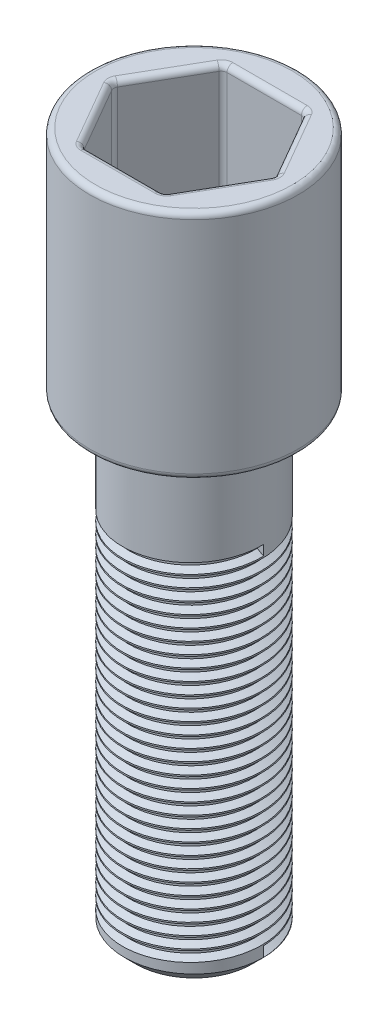
SolidWorks part; units mm, degrees
material "AISI 4140 Steel, quenched & tempered"
ref_plane "Front Plane" through (0, 0, 0) normal (1, 0, 0) x (0, 1, 0)
ref_plane "Top Plane" through (0, 0, 0) normal (0, 0, 1) x (0, 1, 0)
ref_plane "Right Plane" through (0, 0, 0) normal (0, 1, 0) x (-1, 0, 0)
sketch "Sketch1" plane through (0, 0, 0) normal (1, 0, 0) x (0, 1, 0)
  line L0 (-122.9929, 0) -> (42.9358, 0) construction
  line L1 (0, 23.268) -> (0, -20.4189) construction
  line L2 (10, 0) -> (10, 4.5)
  line L3 (10, 4.5) -> (0, 4.5)
  line L4 (0, 4.5) -> (0, 3)
  line L5 (0, 3) -> (-20, 3)
  line L6 (-20, 3) -> (-20, 0)
  line L7 (-20, 0) -> (10, 0)
  dimension "D1" = 10
  dimension "D2" = 9
  dimension "D3" = 6
  dimension "D4" = 20
revolve "Revolve1" add sketch "Sketch1" angle 360 about L0
sketch "Sketch2" plane through (0, 10, 0) normal (0, 1, 0) x (-1, 0, 0)
  line L1 (1.75, -3.0311) -> (3.5, 0)
  line L2 (3.5, 0) -> (1.75, 3.0311)
  line L3 (1.75, 3.0311) -> (-1.75, 3.0311)
  line L4 (-1.75, 3.0311) -> (-3.5, 0)
  line L5 (-3.5, 0) -> (-1.75, -3.0311)
  line L6 (-1.75, -3.0311) -> (1.75, -3.0311)
  circle A0 centre (0, 0) radius 3.0311 construction
  dimension "D1" = 3.5
extrude "Cut-Extrude1" cut sketch "Sketch2" against normal blind 8
ref_axis "Axis1" through (0, 16, 0) along (0, -1, 0)
thread "Thread2" pitch 0.5 method cut profile "Thread Profile2" start angle 0, offset 0.5, length 15, pitch 0.5, diameter 6
ref_plane "Plane2" through (3, -19.5, 0) normal (0, 0, 1) x (1, 0, 0)
sketch "Thread Profile2" plane through (3, -19.5, 0) normal (0, 0, 1) x (1, 0, 0)
  line L0 (0, 0) -> (0, 0.5) construction
  line L11 (0, 0) -> (0, 0.4375)
  line L12 (0, 0.4375) -> (-0.2706, 0.2812)
  line L13 (-0.2706, 0.2812) -> (-0.2706, 0.1562)
  line L15 (-0.2706, 0.1562) -> (0, 0)
  line L17 (-0.2706, 0.2187) -> (0, 0.2187) construction
  point P2 (0, 0)
  dimension "Pitch" = 0.5
  dimension "Profile_Angle" = 60
  dimension "Profile_Land" = 0.125
  dimension "Profile_Height" = 0.2706
chamfer "Chamfer1" distance 0.5 angle 45 1 edges at (0, -20, -3)
fillet "Fillet1" radius 0.25 20 edges at (0, 0, -4.5) (0, 10, -4.5) (0, 10, -3.0311) (-2.625, 10, -1.5155) (-2.625, 10, 1.5155) (0, 10, 3.0311) (2.625, 10, 1.5155) (2.625, 10, -1.5155) (0, 2, -3.0311) (-2.625, 2, -1.5155) (-2.625, 2, 1.5155) (0, 2, 3.0311) (2.625, 2, 1.5155) (2.625, 2, -1.5155) (-1.75, 6, -3.0311) (-1.75, 6, 3.0311) (1.75, 6, 3.0311) (3.5, 6, 0) (1.75, 6, -3.0311) (-3.5, 6, 0)
